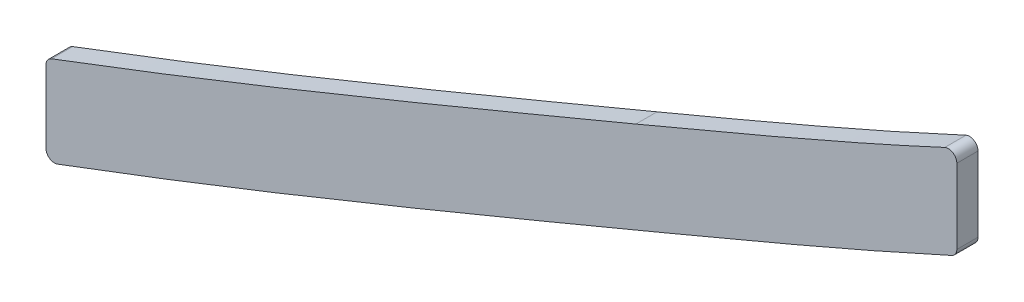
SolidWorks part; units mm, degrees
material "Balsa"
ref_plane "Front Plane" through (0, 0, 0) normal (0, 0, 1) x (1, 0, 0)
ref_plane "Top Plane" through (0, 0, 0) normal (0, 1, 0) x (1, 0, 0)
ref_plane "Right Plane" through (0, 0, 0) normal (1, 0, 0) x (0, 0, -1)
sketch "Sketch1" plane through (0, 0, 0) normal (0, 0, 1) x (1, 0, 0)
  line L0 (129.1265, 126.0779) -> (45.2335, 95.7177) construction
  line L1 (0, 0) -> (0, 656.1291) construction
  line L2 (1046.2855, -53.4707) -> (499.61, -53.4707)
  line L3 (210.5585, 160.3278) -> (162.5016, 140.2562) construction
  line L4 (103.1875, 116.7756) -> (103.1875, 13.8211)
  line L5 (239.7125, 173.3723) -> (239.7125, 18.8603)
  line L6 (239.2308, 173.1465) -> (239.7125, 173.3723)
  line L8 (244.6214, 161.6473) -> (245.1031, 161.8731) construction
  arc A3 (36.5452, 91.5722) -> (50.6762, 98.5918) centre (72.503, 36.9197) cw
  arc A4 (33.5941, 89.512) -> (36.5452, 91.5722) centre (72.5029, 36.9192) cw
  arc A5 (26.5879, 83.5209) -> (26.7433, 83.6735) centre (72.5028, 36.9189) cw
  spline S0 degree 3 poles (90.5238, 112.1079) (125.4792, 124.758) (161.5722, 139.868) (191.6078, 152.4128) knots 0 0 0 0 1 1 1 1
  spline S1 degree 1 poles (94.8455, 100.1658) (196.5024, 140.6938) knots 0 0 1 1 construction
  spline S2 degree 1 poles (196.5024, 140.6938) (244.6214, 161.6473) knots 0 0 1 1 construction
  spline S3 degree 3 poles (94.8455, 100.1658) (99.2852, 101.7725) (108.1262, 105.0368) (121.4387, 110.1165) (134.6545, 115.2971) (147.7092, 120.5264) (160.5147, 125.7437) (170.9096, 130.0328) (179.0169, 133.3991) (184.9834, 135.8842) (189.8481, 137.9146) (193.6777, 139.514) (195.5579, 140.2994) (196.5024, 140.6938) knots 0 0 0 0 0.125 0.25 0.375 0.5 0.625 0.75 0.8125 0.875 0.9375 0.96875 1 1 1 1
  spline S4 degree 3 poles (196.5024, 140.6938) (200.4723, 142.3519) (208.3835, 145.6702) (220.3642, 150.772) (230.4226, 155.1671) (238.5139, 158.8124) (242.5935, 160.6966) (244.6214, 161.6473) knots 14.81781 14.81781 14.81781 14.81781 16.034279 17.250748 18.467217 19.075451 19.683685 19.683685 19.683685 19.683685
  spline S8 degree 5 poles (191.6078, 152.4128) (201.0734, 156.3662) (210.5667, 160.3662) (220.0964, 164.4424) (229.6613, 168.6605) (239.2308, 173.1465) knots 14.81781 14.81781 14.81781 14.81781 14.81781 14.81781 19.683685 19.683685 19.683685 19.683685 19.683685 19.683685 weights 1 1 1 1 1 1
  spline S9 degree 5 poles (50.6762, 98.5918) (58.5981, 101.1149) (66.52, 103.702) (74.4715, 106.3907) (82.4705, 109.1935) (90.5238, 112.1079) knots 0 0 0 0 0 0 4.296847 4.296847 4.296847 4.296847 4.296847 4.296847 weights 1 1 1 1 1 1
  spline S10 degree 5 poles (26.7433, 83.6735) (28.0126, 84.9158) (29.3241, 86.115) (30.6979, 87.2902) (32.127, 88.4267) (33.5941, 89.512) knots 0 0 0 0 0 0 0.963167 0.963167 0.963167 0.963167 0.963167 0.963167 weights 1 1 1 1 1 1
  spline S11 degree 5 poles (18.4363, 73.7529) (19.8463, 75.8225) (21.3553, 77.8246) (22.9948, 79.8016) (24.7465, 81.7067) (26.5879, 83.5209) knots 0 0 0 0 0 0 1.402615 1.402615 1.402615 1.402615 1.402615 1.402615 weights 1 1 1 1 1 1
  spline S12 degree 5 poles (818.067, 264.7065) (827.0431, 263.4992) (836.0291, 262.3734) (845.0868, 261.3058) (891.3865, 256.087) (937.6862, 251.7792) (973.4521, 248.2277) (1071.9467, 239.0511) (1170.4413, 229.7315) (1231.7919, 224.5039) (1324.8993, 216.7906) (1418.0067, 209.0401) (1449.7429, 206.3618) (1636.9286, 190.5211) (1824.1143, 175.4092) (1979.9669, 164.2997) (2156.2686, 150.4144) (2332.5703, 133.8572) (2354.213, 131.7851) (2436.3555, 123.724) (2518.4981, 114.8591) (2579.4813, 107.7425) (2639.6368, 100.3834) (2699.7923, 92.6045) knots 77.930822 77.930822 77.930822 77.930822 77.930822 77.930822 82.465793 82.465793 82.465793 100.79329 100.79329 100.79329 131.098954 131.098954 131.098954 146.769198 146.769198 146.769198 223.533959 223.533959 223.533959 233.943117 233.943117 233.943117 264.216209 264.216209 264.216209 264.216209 264.216209 264.216209 weights 1 1 1 1 1 1 1 1 1 1 1 1 1 1 1 1 1 1 1 1 1 1 1 1
  spline S13 degree 5 poles (241.4251, -53.4707) (224.2869, -53.4707) (207.1495, -53.4673) (190.2039, -52.6866) (151.6561, -49.0319) (113.1083, -41.5037) (91.9499, -36.3426) (71.313, -30.9696) (50.6762, -24.7565) knots 0 0 0 0 0 0 8.713816 8.713816 8.713816 19.90683 19.90683 19.90683 19.90683 19.90683 19.90683 weights 1 1 1 1 1 1 1 1 1
  spline S14 degree 5 poles (499.61, -53.4707) (492.1368, -53.4707) (484.7543, -53.4707) (477.443, -53.4707) (448.5166, -53.4707) (419.5901, -53.4707) (398.3681, -53.4707) (355.6475, -53.4707) (312.927, -53.4707) (289.2351, -53.4703) (265.365, -53.4707) (241.4948, -53.4707) (241.4716, -53.4707) (241.4484, -53.4707) (241.4251, -53.4707) knots 19.90683 19.90683 19.90683 19.90683 19.90683 19.90683 23.637897 23.637897 23.637897 34.276546 34.276546 34.276546 46.401341 46.401341 46.401341 46.413154 46.413154 46.413154 46.413154 46.413154 46.413154 weights 1 1 1 1 1 1 1 1 1 1 1 1 1 1 1
  spline S15 degree 5 poles (2699.7923, -7.5245) (2639.6368, -11.6572) (2579.4813, -15.4358) (2518.4981, -19.1485) (2436.3555, -23.2524) (2354.213, -26.6315) (2332.5703, -27.481) (2156.2686, -34.3778) (1979.9669, -41.6286) (1824.1143, -52.7713) (1636.9286, -53.5796) (1449.7429, -53.454) (1418.0067, -53.4707) (1324.8993, -53.4707) (1231.7919, -53.4707) (1170.4413, -53.4707) (1108.7841, -53.4707) (1047.1269, -53.4707) (1046.8464, -53.4707) (1046.5659, -53.4707) (1046.2855, -53.4707) knots 100.654805 100.654805 100.654805 100.654805 100.654805 100.654805 130.927897 130.927897 130.927897 141.337055 141.337055 141.337055 218.101815 218.101815 218.101815 233.772059 233.772059 233.772059 264.077723 264.077723 264.077723 264.216209 264.216209 264.216209 264.216209 264.216209 264.216209 weights 1 1 1 1 1 1 1 1 1 1 1 1 1 1 1 1 1 1 1 1 1
  point P2 (0, 0)
  point P9 (0, 0)
  dimension "D1" = 72.503
  dimension "D2" = 1046.2855
  dimension "D3" = 818.067
  dimension "D4" = 103.1875
  dimension "D5" = 239.7125
  dimension "D6" = 12.7
extrude "Boss-Extrude1" add sketch "Sketch1" against normal mid plane 3.175 contours S8 S0 L4 S3 S4 L5 L6 region at (171.7204, 137.53, 0)
fillet "Fillet1" radius 1.27 4 edges at (239.7125, 159.3721, 0) (239.7125, 173.3723, 0) (103.1875, 103.2218, 0) (103.1875, 116.7756, 0)
